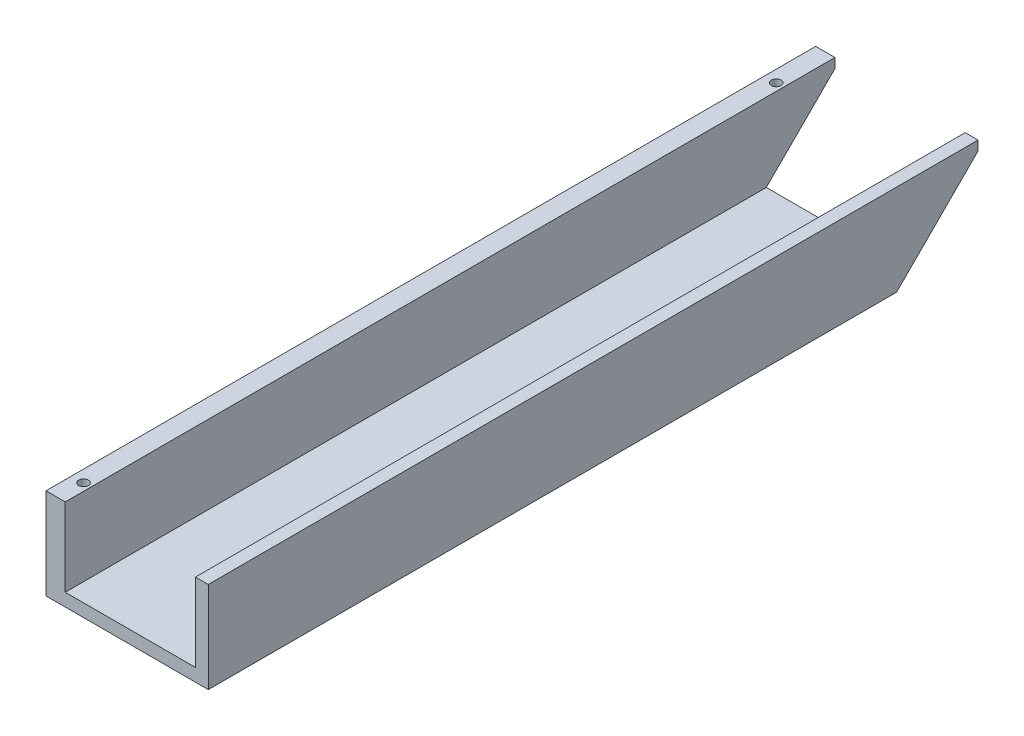
SolidWorks part; units mm, degrees
ref_plane "Front Plane" through (0, 0, 0) normal (0, 0, 1) x (1, 0, 0)
ref_plane "Top Plane" through (0, 0, 0) normal (0, 1, 0) x (1, 0, 0)
ref_plane "Right Plane" through (0, 0, 0) normal (1, 0, 0) x (0, 0, -1)
ref_axis "X-Axis" through (0, 0, 0) along (1, 0, 0)
ref_axis "Y-Axis" through (0, 42.2917, 0) along (0, -1, 0)
ref_axis "Z-Axis" through (0, 0, 55.0015) along (0, 0, -1)
sketch "Sketch1" plane through (0, 0, 0) normal (0, 0, 1) x (1, 0, 0)
  line L0 (-8.0089, 6.7786) -> (-5.0089, 6.7786)
  line L1 (-5.0089, 6.7786) -> (-5.0089, -5.4214)
  line L2 (-5.0089, -5.4214) -> (15.2911, -5.4214)
  line L3 (15.2911, -5.4214) -> (15.2911, 6.7786)
  line L4 (15.2911, 6.7786) -> (17.2911, 6.7786)
  line L5 (17.2911, 6.7786) -> (17.2911, -7.4214)
  line L6 (17.2911, -7.4214) -> (-8.0089, -7.4214)
  line L7 (-8.0089, -7.4214) -> (-8.0089, 6.7786)
  line L8 (-0.8459, -4.4214) -> (52.4677, -4.4214) construction
  line L9 (52.4677, -4.4214) -> (52.4677, 5.5786) construction
  line L10 (52.4677, 5.5786) -> (-1.8799, 5.5786) construction
  dimension "D1" = 3
  dimension "D2" = 2
  dimension "D3" = 20.3
  dimension "D4" = 2
  dimension "D5" = 14.2
  dimension "Largeur_Rail" = 25.3
  dimension "Profondeur_Rail" = 12.2
extrude "Rail-Extrude" add sketch "Sketch1" along normal blind 120
sketch "Sketch2" plane through (0, 6.7786, 0) normal (0, 1, 0) x (1, 0, 0)
  line L0 (-6.1589, 0) -> (-6.1589, -8) construction
  line L1 (-5.0089, 0) -> (-8.0089, 0) construction
  line L2 (-8.0089, -120) -> (-8.0089, 0) construction
  circle A0 centre (-6.1589, -8) radius 0.75
  dimension "D1" = 1.5
  dimension "D2" = 8
  dimension "D3" = 1.85
extrude "First Hole" cut sketch "Sketch2" against normal through all
sketch "Sketch3" plane through (0, 6.7786, 0) normal (0, 1, 0) x (1, 0, 0)
  line L0 (-6.1589, -8) -> (-6.1589, -116) construction
  circle A0 centre (-6.1589, -116) radius 0.75
  circle A1 centre (-6.1589, -8) radius 0.75 construction
  dimension "D1" = 108
extrude "Last Hole" cut sketch "Sketch3" against normal through all
sketch "Sketch5" plane through (-8.0089, 0, 0) normal (-1, 0, 0) x (0, 0, 1)
  line L5 (120, 6.7786) -> (0, 6.7786) construction
  line L6 (120, -7.4214) -> (0, -7.4214) construction
  line L7 (0, -5.4214) -> (10, -5.4214) construction
  line L8 (0, -5.4214) -> (0, -7.4214) construction
  line L9 (0, -7.4214) -> (10, -7.4214) construction
  line L10 (10, -5.4214) -> (10, -7.4214) construction
  line L11 (0, 6.7786) -> (0, -7.4214) construction
  line L12 (12.7, -7.4214) -> (0, 5.2786)
  line L13 (0, 5.2786) -> (0, -7.4214)
  line L14 (0, -7.4214) -> (12.7, -7.4214)
  dimension "D1" = 2
  dimension "D2" = 10
  dimension "D3" = 45
  dimension "D4" = 1.5
extrude "Angle" cut sketch "Sketch5" against normal through all
equation "\"Largeur Bande\"= 24.3"
equation "\"Largeur_Rail\"= \"Largeur Bande\" + 1"
equation "\"Profondeur Bande\"= 12"
equation "\"Profondeur_Rail\" = \"Profondeur Bande\" + 0.2"
equation "\"Largeur Feeder\"= \"Largeur Rail\" + 1.2 + 1.2 + 0.3"
equation "\"Largeur Rail\"= \"Largeur Bande\" + 1"
equation "\"D1@Boss-Extrude1\"=\"Largeur Feeder\"/2"
equation "\"D2@Boss-Extrude1\"=\"Largeur Feeder\"/2"
